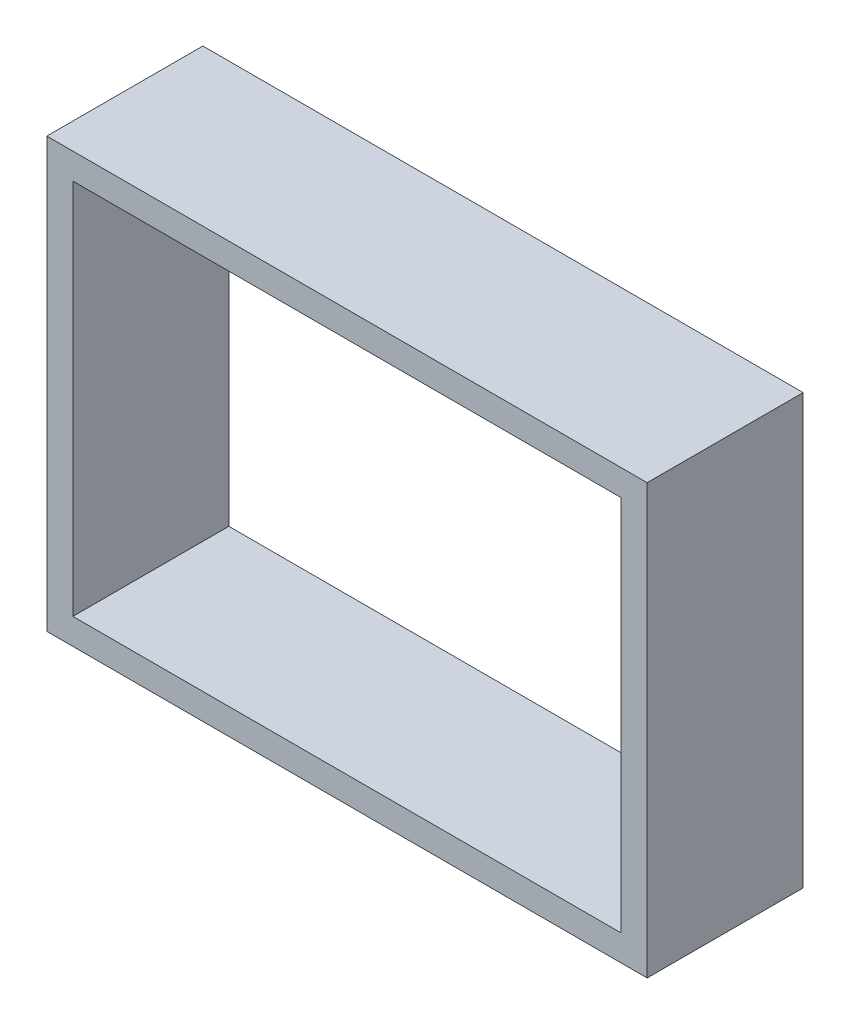
SolidWorks part; units mm, degrees
ref_plane "Alzado" through (0, 0, 0) normal (0, 0, 1) x (1, 0, 0)
ref_plane "Planta" through (0, 0, 0) normal (0, 1, 0) x (1, 0, 0)
ref_plane "Vista lateral" through (0, 0, 0) normal (1, 0, 0) x (0, 0, -1)
sketch "Croquis1" plane through (0, 0, 0) normal (0, 0, 1) x (1, 0, 0)
  line L0 (36.0507, -11.25) -> (-52.3115, -11.25) construction
  line L1 (36.0507, -11.25) -> (36.0507, 50.75) construction
  line L2 (-52.3115, -11.25) -> (-52.3115, 50.75) construction
  line L3 (36.0507, 50.75) -> (-52.3115, 50.75) construction
  line L4 (38.0507, -13.25) -> (-54.3115, -13.25)
  line L5 (-54.3115, -13.25) -> (-54.3115, 52.75)
  line L6 (38.0507, 52.75) -> (-54.3115, 52.75)
  line L7 (38.0507, -13.25) -> (38.0507, 52.75)
  line L8 (34.0507, -9.25) -> (-50.3115, -9.25)
  line L9 (-50.3115, -9.25) -> (-50.3115, 48.75)
  line L10 (34.0507, 48.75) -> (-50.3115, 48.75)
  line L11 (34.0507, -9.25) -> (34.0507, 48.75)
  line L12 (15.5, -9.25) -> (-18.5, -9.25) construction
  dimension "D4" = 58
  dimension "D5" = 0
  dimension "D1" = 2
  dimension "D2" = 2
extrude "Saliente-Extruir1" add sketch "Croquis1" against normal blind 23 and the other way blind 1
sketch "Croquis2" plane through (0, -13.25, 0) normal (0, -1, 0) x (-1, 0, 0)
  line L0 (48.7666, -1) -> (48.7666, 23) construction
  line L1 (54.3115, -1) -> (-38.0507, -1) construction
  line L2 (54.3115, 23) -> (-38.0507, 23) construction
  circle A0 centre (48.7666, 3.9048) radius 4
  point P8 (40.2124, 11)
  point P10 (40.2124, 11)
  point P12 (40.2124, 11)
  point P13 (0, 0)
  point P14 (40.2124, 11)
  point P15 (40.2124, 15.9869)
  point P16 (48.623, 18.296)
  point P17 (37.4355, 3.9048)
  point P18 (48.7666, 3.1819)
extrude "Cortar-Extruir1" cut sketch "Croquis2" against normal blind 2
